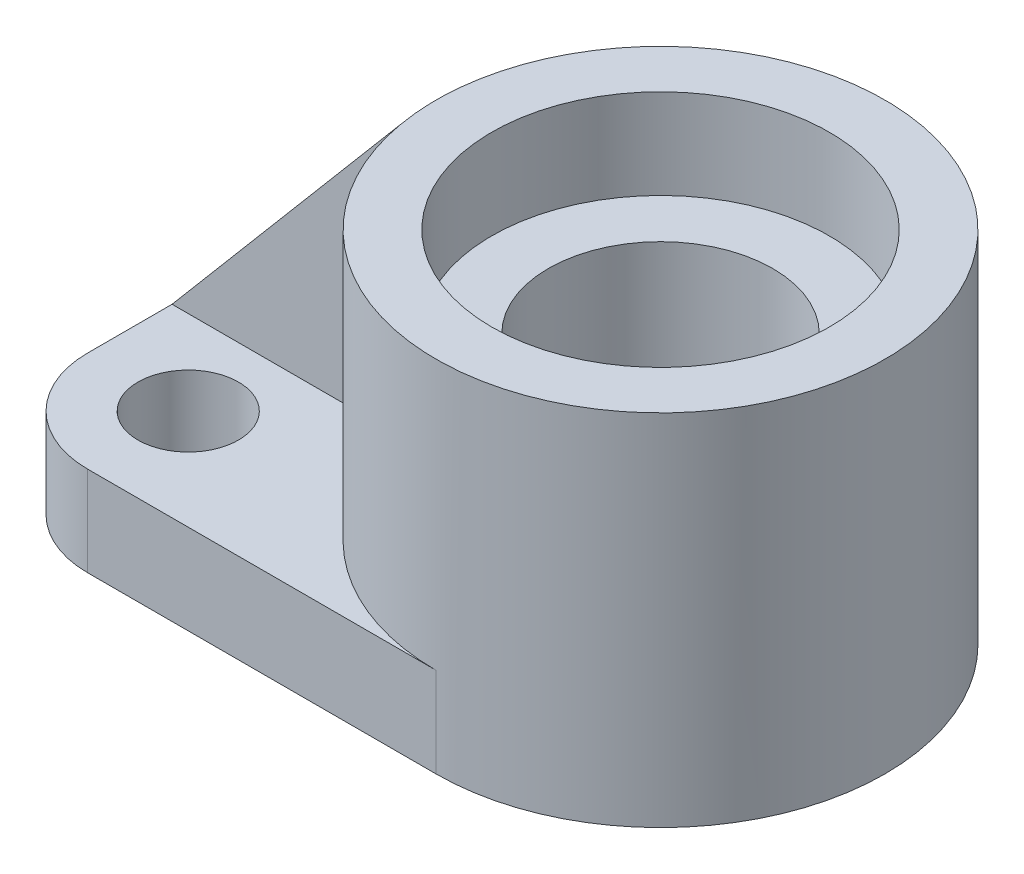
SolidWorks part; units mm, degrees
ref_plane "Front Plane" through (0, 0, 0) normal (0, 0, 1) x (1, 0, 0)
ref_plane "Top Plane" through (0, 0, 0) normal (0, 1, 0) x (1, 0, 0)
ref_plane "Right Plane" through (0, 0, 0) normal (1, 0, 0) x (0, 0, -1)
sketch "Sketch1" plane through (0, 0, 0) normal (0, 1, 0) x (1, 0, 0)
  line L0 (-69, -125) -> (125, -125)
  line L1 (-125, -69) -> (-125, 69)
  line L2 (125, -125) -> (125, 125) construction
  line L3 (-69, 125) -> (125, 125)
  line L4 (-125, -125) -> (125, 125) construction
  line L5 (125, -125) -> (-125, 125) construction
  circle A0 centre (125, 0) radius 125
  circle A1 centre (125, 0) radius 94
  circle A2 centre (125, 0) radius 62.5
  arc A3 (-69, -125) -> (-125, -69) centre (-69, -69) cw
  arc A4 (-69, 125) -> (-125, 69) centre (-69, 69) ccw
  circle A5 centre (-69, 69) radius 28
  circle A6 centre (-69, -69) radius 28
  point P1 (0, 0)
  dimension "D2" = 250
  dimension "D3" = 188
  dimension "D4" = 125
  dimension "D5" = 56
  dimension "D6" = 56
  dimension "D1" = 250
extrude "Boss-Extrude1" add sketch "Sketch1" along normal blind 50 contours L3 A4 L1 A3 L0 A0 A6 A5 region at (-40.2272, 0, 0)
extrude "Boss-Extrude2" add sketch "Sketch1<3>" along normal blind 200 contours A0
sketch "Sketch1<3>" plane through (0, 0, 0) normal (0, 1, 0) x (1, 0, 0) same geometry as "Sketch1"
hole_wizard "CBORE for M5 Hex Head Bolt1" positions "Sketch4" profile "Sketch3" counterbore size "M5" standard "ISO"
sketch "Sketch4" plane through (0, 200, 0) normal (0, 1, 0) x (1, 0, 0)
  point P0 (125, 0)
sketch "Sketch3" plane through (125, 200, 0) normal (1, 0, 0) x (0, 0, 1)
  line L0 (0, 0) -> (0, 236.0844)
  line L1 (0, 236.0844) -> (62.5, 200)
  line L2 (62.5, 200) -> (62.5, 50)
  line L3 (62.5, 50) -> (94, 50)
  line L4 (94, 50) -> (94, 0)
  line L5 (94, 0) -> (0, 0)
  line L10 (0, 236.0844) -> (-62.5, 200) construction
  line L11 (0, -6.35) -> (0, 107.95) construction
  dimension "Hole Dia." = 125
  dimension "Hole Depth" = 200
  dimension "C'Bore Dia." = 188
  dimension "C'Bore Depth" = 50
  dimension "Drill Angle" = 120
sketch "Sketch6" plane through (0, 200, 0) normal (0, 1, 0) x (1, 0, 0)
  line L0 (1.9512, -22) -> (26.9385, -22)
  line L2 (26.9385, -22) -> (26.9385, 22)
  line L3 (1.9512, 22) -> (26.9385, 22)
  line L4 (0, 0) -> (26.9385, 22) construction
  line L5 (26.9385, -22) -> (0, 0) construction
  arc A0 (1.9512, 22) -> (1.9512, -22) centre (125, 0) ccw
  point P1 (0, 0)
  point P3 (26.9385, -22)
sketch "Sketch7" plane through (0, 50, 0) normal (0, 1, 0) x (1, 0, 0)
  line L0 (-125, -69) -> (-125, 69) construction
  line L1 (-125, 22) -> (19.117, 22)
  line L2 (-125, 22) -> (-125, -22)
  line L3 (-125, -22) -> (19.117, -22)
  line L4 (19.117, 22) -> (19.117, -22)
  point P6 (-125, 0)
  point P7 (-125, 0)
  point P8 (19.117, -22)
  dimension "D1" = 44
loft "Loft1" add profiles "Sketch7", "Sketch6"
